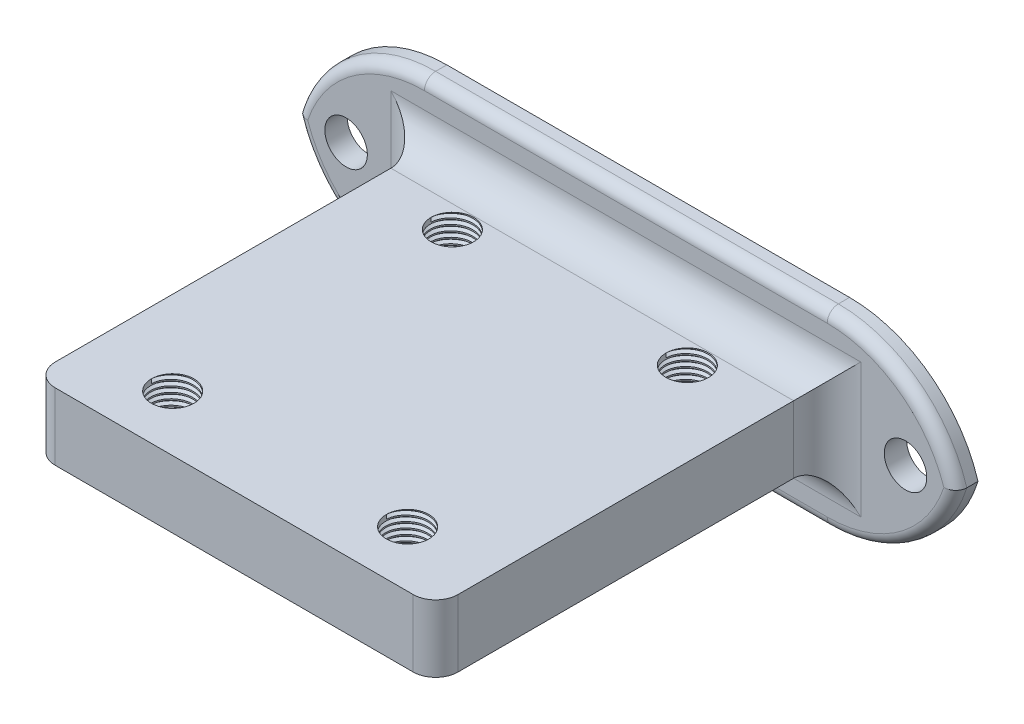
SolidWorks part; units mm, degrees
ref_plane "Alzado" through (0, 0, 0) normal (0, 0, 1) x (1, 0, 0)
ref_plane "Planta" through (0, 0, 0) normal (0, 1, 0) x (1, 0, 0)
ref_plane "Vista lateral" through (0, 0, 0) normal (1, 0, 0) x (0, 0, -1)
sketch "Croquis1" plane through (0, 0, 0) normal (0, 0, 1) x (1, 0, 0)
  line L1 (18, -3) -> (-18, -3)
  line L2 (18, -3) -> (18, 3)
  line L3 (18, 3) -> (-18, 3)
  line L4 (-18, -3) -> (-18, 3)
  line L5 (18, -3) -> (-18, 3) construction
  line L6 (18, 3) -> (-18, -3) construction
  point P0 (0, 0)
  dimension "D1" = 6
  dimension "D2" = 36
extrude "Saliente-Extruir1" add sketch "Croquis1" along normal blind 35
sketch "Croquis3" plane through (0, -3, 0) normal (0, -1, 0) x (1, 0, 0)
  line L0 (-18, 35) -> (-18, 0) construction
  line L1 (-18, 35) -> (18, 35) construction
  line L2 (0, 35) -> (0, 0) construction
  line L3 (0, 17.5) -> (-18, 17.5) construction
  circle A0 centre (-10.5, 30) radius 1.9
  circle A1 centre (-10.5, 5) radius 1.9
  circle A2 centre (10.5, 5) radius 1.9
  circle A3 centre (10.5, 30) radius 1.9
  dimension "D1" = 3.8
  dimension "D2" = 7.5
  dimension "D3" = 5
extrude "Cortar-Extruir1" cut sketch "Croquis3" against normal through all
ref_plane "Plano1" through (0, 0, -2) normal (0, 0, -1) x (-1, 0, 0)
sketch "Croquis4" plane through (0, 0, -2) normal (0, 0, -1) x (-1, 0, 0)
  line L1 (30, 8.5) -> (-30, 8.5)
  line L2 (30, 8.5) -> (30, -8.5)
  line L3 (30, -8.5) -> (-30, -8.5)
  line L4 (-30, 8.5) -> (-30, -8.5)
  line L5 (30, 8.5) -> (-30, -8.5) construction
  line L6 (30, -8.5) -> (-30, 8.5) construction
  point P0 (0, 0)
  dimension "D1" = 60
  dimension "D2" = 17
extrude "Saliente-Extruir2" add sketch "Croquis4" against normal blind 2
fillet "Redondeo1" radius 2 2 edges at (-18, 0, 35) (18, 0, 35)
sketch "Croquis5" plane through (0, 0, 0) normal (0, 0, 1) x (1, 0, 0)
  line L0 (0, 0) -> (0, -3) construction
  line L2 (-16, -3) -> (16, -3) construction
  circle A0 centre (25, 0) radius 1.9
  circle A1 centre (-25, 0) radius 1.9
  dimension "D1" = 3.8
  dimension "D4" = 25
extrude "Cortar-Extruir2" cut sketch "Croquis5" against normal through all
fillet "Redondeo2" radius 3 4 edges at (0, -3, 0) (-18, 0, 0) (18, 0, 0) (0, 3, 0)
fillet "Redondeo4" radius 12 4 edges at (-30, -8.5, -1) (-30, 8.5, -1) (30, -8.5, -1) (30, 8.5, -1)
fillet "Redondeo3" radius 1 6 edges at (0, -8.5, 0) (0, 8.5, 0) (25.1414, -6.1437, 0) (-25.1414, -6.1437, 0) (-25.1414, 6.1437, 0) (25.1414, 6.1437, 0)
thread "Rosca1" pitch 0.5 method cut profile "Perfil de rosca1" start angle 0, offset 0, length 0, pitch 0.5, diameter 3.8
ref_plane "Plano2" through (8.6, 3, 30) normal (0, 0, 1) x (-1, 0, 0)
sketch "Perfil de rosca1" plane through (8.6, 3, 30) normal (0, 0, 1) x (-1, 0, 0)
  line L0 (0, 0) -> (0, 0.5) construction
  line L1 (0, 0) -> (0.2706, 0.1562)
  line L2 (0.2706, 0.1562) -> (0.2706, 0.2187)
  line L3 (0.2706, 0.2187) -> (0, 0.375)
  line L4 (0.2706, 0.1875) -> (0, 0.1875) construction
  line L11 (0, 0) -> (0, 0.375)
  point P2 (0, 0)
  dimension "Pitch" = 0.5
  dimension "Profile_Angle" = 60
  dimension "Profile_Land" = 0.0625
  dimension "Profile_Height" = 0.2706
thread "Rosca2" pitch 0.5 method cut profile "Perfil de rosca2" start angle 0, offset 0, length 0, pitch 0.5, diameter 3.8
ref_plane "Plano3" through (-12.4, 3, 30) normal (0, 0, 1) x (-1, 0, 0)
sketch "Perfil de rosca2" plane through (-12.4, 3, 30) normal (0, 0, 1) x (-1, 0, 0)
  line L0 (0, 0) -> (0, 0.5) construction
  line L1 (0, 0) -> (0.2706, 0.1562)
  line L2 (0.2706, 0.1562) -> (0.2706, 0.2187)
  line L3 (0.2706, 0.2187) -> (0, 0.375)
  line L4 (0.2706, 0.1875) -> (0, 0.1875) construction
  line L11 (0, 0) -> (0, 0.375)
  point P2 (0, 0)
  dimension "Pitch" = 0.5
  dimension "Profile_Angle" = 60
  dimension "Profile_Land" = 0.0625
  dimension "Profile_Height" = 0.2706
thread "Rosca3" pitch 0.5 method cut profile "Perfil de rosca3" start angle 0, offset 0, length 0, pitch 0.5, diameter 3.8
ref_plane "Plano4" through (-12.4, 3, 5) normal (0, 0, 1) x (-1, 0, 0)
sketch "Perfil de rosca3" plane through (-12.4, 3, 5) normal (0, 0, 1) x (-1, 0, 0)
  line L0 (0, 0) -> (0, 0.5) construction
  line L1 (0, 0) -> (0.2706, 0.1562)
  line L2 (0.2706, 0.1562) -> (0.2706, 0.2187)
  line L3 (0.2706, 0.2187) -> (0, 0.375)
  line L4 (0.2706, 0.1875) -> (0, 0.1875) construction
  line L11 (0, 0) -> (0, 0.375)
  point P2 (0, 0)
  dimension "Pitch" = 0.5
  dimension "Profile_Angle" = 60
  dimension "Profile_Land" = 0.0625
  dimension "Profile_Height" = 0.2706
thread "Rosca4" pitch 0.5 method cut profile "Perfil de rosca4" start angle 0, offset 0, length 0, pitch 0.5, diameter 3.8
ref_plane "Plano5" through (8.6, 3, 5) normal (0, 0, 1) x (-1, 0, 0)
sketch "Perfil de rosca4" plane through (8.6, 3, 5) normal (0, 0, 1) x (-1, 0, 0)
  line L0 (0, 0) -> (0, 0.5) construction
  line L1 (0, 0) -> (0.2706, 0.1562)
  line L2 (0.2706, 0.1562) -> (0.2706, 0.2187)
  line L3 (0.2706, 0.2187) -> (0, 0.375)
  line L4 (0.2706, 0.1875) -> (0, 0.1875) construction
  line L11 (0, 0) -> (0, 0.375)
  point P2 (0, 0)
  dimension "Pitch" = 0.5
  dimension "Profile_Angle" = 60
  dimension "Profile_Land" = 0.0625
  dimension "Profile_Height" = 0.2706
